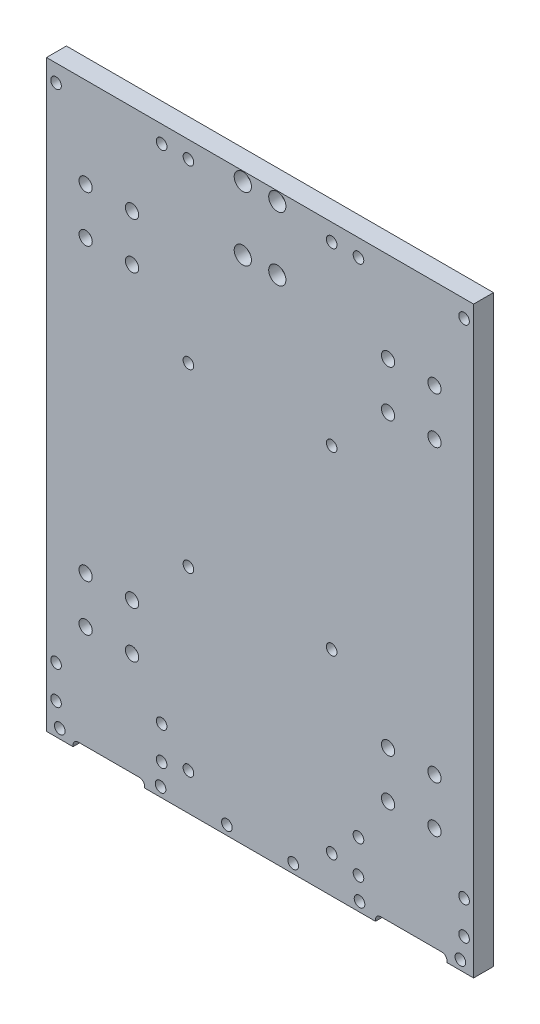
SolidWorks part; units mm, degrees
ref_plane "Płaszczyzna przednia" through (0, 0, 0) normal (0, 0, 1) x (1, 0, 0)
ref_plane "Płaszczyzna górna" through (0, 0, 0) normal (0, 1, 0) x (1, 0, 0)
ref_plane "Płaszczyzna prawa" through (0, 0, 0) normal (1, 0, 0) x (0, 0, -1)
sketch "Szkic1" plane through (0, 0, 0) normal (0, 0, 1) x (1, 0, 0)
  line L1 (161, -220) -> (-161, -220)
  line L2 (161, -220) -> (161, 220)
  line L3 (161, 220) -> (-161, 220)
  line L4 (-161, -220) -> (-161, 220)
  line L5 (161, -220) -> (-161, 220) construction
  line L6 (161, 220) -> (-161, -220) construction
  point P0 (0, 0)
  dimension "D1" = 322
  dimension "D2" = 440
extrude "Dodanie-wyciągnięcie1" add sketch "Szkic1" along normal blind 15
sketch "Szkic2" plane through (0, 0, 15) normal (0, 0, 1) x (1, 0, 0)
  line L0 (161, 220) -> (-161, 220) construction
  line L1 (-161, 220) -> (-161, -220) construction
  circle A0 centre (-131.5, 152) radius 3
  dimension "D1" = 68
  dimension "D3" = 6
  dimension "D2" = 29.5
extrude "Wytnij-wyciągnięcie1" cut sketch "Szkic2" against normal blind 15
sketch "Szkic3" plane through (0, 0, 15) normal (0, 0, 1) x (1, 0, 0)
  circle A0 centre (-131.5, 152) radius 5
  dimension "D1" = 10
extrude "Wytnij-wyciągnięcie2" cut sketch "Szkic3" against normal blind 7
pattern_linear "Szyk liniowy1" count 2 spacing 35 along (1, 0, 0) count 2 spacing 35 along (0, -1, 0) of "Wytnij-wyciągnięcie1", "Wytnij-wyciągnięcie2"
pattern_linear "Szyk liniowy2" count 2 spacing 228 along (1, 0, 0) count 2 spacing 254 along (0, -1, 0) of "Szyk liniowy1"
sketch "Szkic6" plane through (0, 0, 15) normal (0, 0, 1) x (1, 0, 0)
  line L0 (-161, 220) -> (-161, -220) construction
  line L1 (161, 220) -> (-161, 220) construction
  circle A0 centre (-153.8, 207) radius 4
  circle A1 centre (-74.2, 207) radius 4
  dimension "D1" = 8
  dimension "D2" = 8
  dimension "D3" = 7.2
  dimension "D4" = 13
  dimension "D5" = 79.6
extrude "Wytnij-wyciągnięcie3" cut sketch "Szkic6" against normal blind 20
sketch "Szkic7" plane through (0, 0, 15) normal (0, 0, 1) x (1, 0, 0)
  line L0 (-161, 220) -> (-161, -220) construction
  line L1 (-161, -220) -> (161, -220) construction
  circle A0 centre (-153.8, -196.5) radius 4
  circle A1 centre (-153.8, -171.5) radius 4
  circle A2 centre (-74.2, -196.5) radius 4
  circle A3 centre (-74.2, -171.5) radius 4
  dimension "D1" = 8
  dimension "D2" = 8
  dimension "D3" = 8
  dimension "D4" = 8
  dimension "D5" = 7.2
  dimension "D6" = 23.5
  dimension "D7" = 25
  dimension "D8" = 79.6
extrude "Wytnij-wyciągnięcie4" cut sketch "Szkic7" against normal blind 20
sketch "Szkic10" plane through (0, 0, 15) normal (0, 0, 1) x (1, 0, 0)
  line L0 (161, 220) -> (-161, 220) construction
  line L1 (161, -220) -> (161, 220) construction
  circle A0 centre (74.2, 207) radius 4
  circle A1 centre (153.8, 207) radius 4
  dimension "D1" = 8
  dimension "D2" = 8
  dimension "D3" = 79.6
  dimension "D4" = 13
  dimension "D5" = 7.2
extrude "Wytnij-wyciągnięcie5" cut sketch "Szkic10" against normal blind 21
sketch "Szkic11" plane through (0, 0, 15) normal (0, 0, 1) x (1, 0, 0)
  line L0 (161, -220) -> (161, 220) construction
  line L2 (-161, -220) -> (161, -220) construction
  circle A0 centre (153.8, -171.5) radius 4
  circle A1 centre (153.8, -196.5) radius 4
  circle A2 centre (74.2, -196.5) radius 4
  circle A3 centre (74.2, -171.5) radius 4
  dimension "D1" = 7.2
  dimension "D5" = 8
  dimension "D6" = 8
  dimension "D7" = 8
  dimension "D8" = 8
  dimension "D2" = 23.5
  dimension "D3" = 25
  dimension "D4" = 79.6
extrude "Wytnij-wyciągnięcie6" cut sketch "Szkic11" against normal blind 21
sketch "Szkic12" plane through (0, 0, 15) normal (0, 0, 1) x (1, 0, 0)
  line L0 (161, 220) -> (-161, 220) construction
  circle A0 centre (-13, 213) radius 4
  circle A1 centre (-74.2, 207) radius 4 construction
  circle A2 centre (13, 213) radius 4
  circle A3 centre (-13, 165) radius 4
  circle A4 centre (13, 165) radius 4
  dimension "D1" = 7
  dimension "D3" = 26
  dimension "D4" = 48
  dimension "D5" = 8
  dimension "D6" = 8
  dimension "D7" = 8
  dimension "D8" = 8
  dimension "D2" = 61.2
extrude "Wytnij-wyciągnięcie7" cut sketch "Szkic12" against normal blind 15
sketch "Szkic13" plane through (0, 0, 15) normal (0, 0, 1) x (1, 0, 0)
  circle A0 centre (-13, 213) radius 6.5
  circle A1 centre (13, 213) radius 6.5
  circle A2 centre (13, 165) radius 6.5
  circle A3 centre (-13, 165) radius 6.5
  dimension "D1" = 13
  dimension "D2" = 13
  dimension "D3" = 13
  dimension "D4" = 13
extrude "Wytnij-wyciągnięcie8" cut sketch "Szkic13" against normal blind 9
sketch "Szkic14" plane through (0, 0, 15) normal (0, 0, 1) x (1, 0, 0)
  line L0 (161, 220) -> (-161, 220) construction
  line L1 (-161, 220) -> (-161, -220) construction
  circle A0 centre (-54, 207) radius 4
  circle A1 centre (54, 207) radius 4
  dimension "D1" = 13
  dimension "D4" = 8
  dimension "D5" = 8
  dimension "D2" = 107
  dimension "D3" = 108
extrude "Wytnij-wyciągnięcie9" cut sketch "Szkic14" against normal blind 15
pattern_linear "Szyk liniowy3" count 4 spacing 133 along (0, -1, 0) of "Wytnij-wyciągnięcie9"
sketch "Szkic22" plane through (0, -220, 0) normal (0, -1, 0) x (1, 0, 0)
  line L0 (-161, 15) -> (83, 15) construction
  line L1 (-141, 15) -> (-87, 15)
  line L2 (-141, 15) -> (-141, 0)
  line L3 (-141, 0) -> (-87, 0)
  line L4 (-87, 15) -> (-87, 0)
  line L5 (-161, 0) -> (83, 0) construction
  line L6 (-161, 15) -> (-161, 0) construction
  dimension "D1" = 20
  dimension "D2" = 54
extrude "Wytnij-wyciągnięcie11" cut sketch "Szkic22" against normal blind 5
sketch "Szkic24" plane through (0, -220, 0) normal (0, -1, 0) x (1, 0, 0)
  line L0 (-87, 15) -> (161, 15) construction
  line L1 (87, 15) -> (141, 15)
  line L2 (87, 15) -> (87, 0)
  line L3 (87, 0) -> (141, 0)
  line L4 (141, 15) -> (141, 0)
  line L5 (-87, 0) -> (161, 0) construction
  line L6 (161, 15) -> (161, 0) construction
  dimension "D1" = 20
  dimension "D2" = 54
extrude "Wytnij-wyciągnięcie13" cut sketch "Szkic24" against normal blind 5
fillet "Zaokrąglenie2" radius 4 4 edges at (87, -215, 7.5) (141, -215, 7.5) (-87, -215, 7.5) (-141, -215, 7.5)
sketch "Szkic25" plane through (0, 0, 15) normal (0, 0, 1) x (1, 0, 0)
  line L0 (-161, -220) -> (-141, -220) construction
  line L1 (-161, 220) -> (-161, -220) construction
  line L2 (141, -220) -> (161, -220) construction
  line L4 (161, -220) -> (161, 220) construction
  circle A0 centre (-151, -213) radius 4
  circle A1 centre (151, -213) radius 4
  dimension "D1" = 7
  dimension "D3" = 8
  dimension "D4" = 8
  dimension "D2" = 10
  dimension "D5" = 7
  dimension "D6" = 10
extrude "Wytnij-wyciągnięcie14" cut sketch "Szkic25" against normal blind 20
sketch "Szkic26" plane through (0, 0, 15) normal (0, 0, 1) x (1, 0, 0)
  line L0 (-87, -220) -> (87, -220) construction
  line L1 (-87, -219) -> (-87, -220) construction
  circle A0 centre (-75, -213) radius 4
  dimension "D1" = 8
  dimension "D2" = 7
  dimension "D3" = 12
extrude "Wytnij-wyciągnięcie15" cut sketch "Szkic26" against normal blind 20
pattern_linear "Szyk liniowy4" count 4 spacing 50 along (1, 0, 0) of "Wytnij-wyciągnięcie15"
